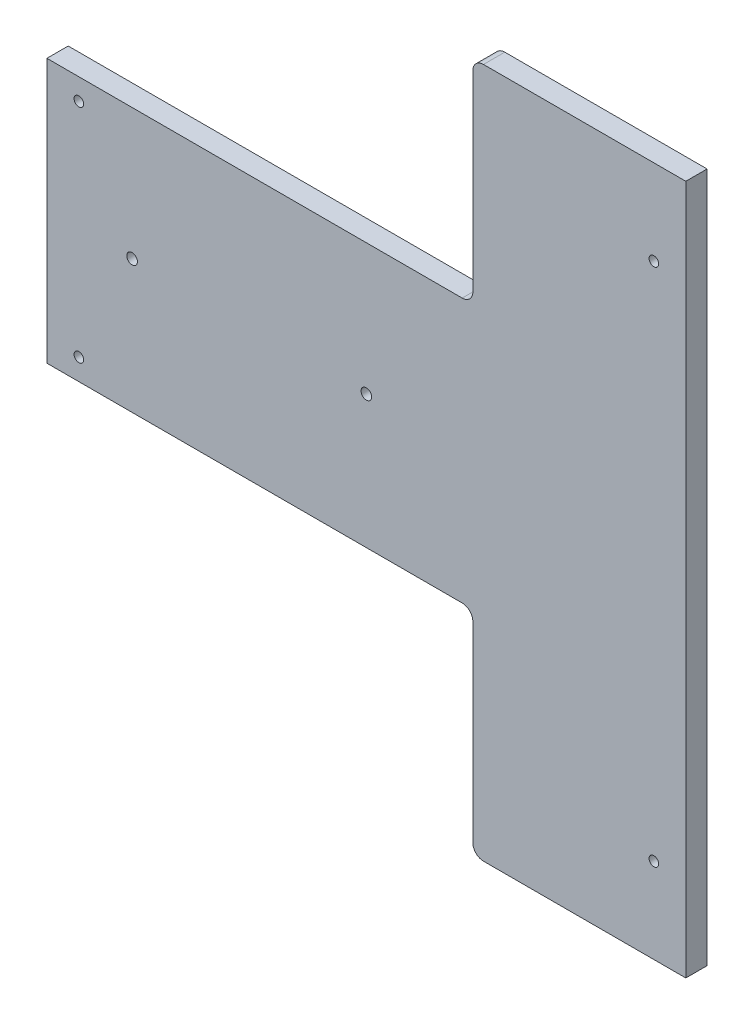
SolidWorks part; units mm, degrees
ref_plane "Plan de face" through (0, 0, 0) normal (0, 0, 1) x (1, 0, 0)
ref_plane "Plan de dessus" through (0, 0, 0) normal (0, 1, 0) x (1, 0, 0)
ref_plane "Plan de droite" through (0, 0, 0) normal (1, 0, 0) x (0, 0, -1)
sketch "Esquisse1" plane through (0, 0, 0) normal (0, 0, 1) x (1, 0, 0)
  line L1 (-122.4446, 41.9355) -> (177.5554, 41.9355)
  line L2 (-122.4446, 41.9355) -> (-122.4446, -82.0645)
  line L3 (-122.4446, -82.0645) -> (177.5554, -82.0645)
  line L4 (177.5554, 41.9355) -> (177.5554, -82.0645)
  line L5 (177.5554, -82.0645) -> (77.5554, -82.0645)
  line L6 (177.5554, -82.0645) -> (177.5554, -182.0645)
  line L7 (177.5554, -182.0645) -> (77.5554, -182.0645)
  line L8 (77.5554, -82.0645) -> (77.5554, -182.0645)
  line L9 (177.5554, 41.9355) -> (77.5554, 41.9355)
  line L10 (177.5554, 41.9355) -> (177.5554, 141.9355)
  line L11 (177.5554, 141.9355) -> (77.5554, 141.9355)
  line L12 (77.5554, 41.9355) -> (77.5554, 141.9355)
  dimension "D1" = 300
  dimension "D2" = 124
  dimension "D3" = 100
  dimension "D4" = 100
  dimension "D5" = 100
  dimension "D6" = 100
extrude "Boss.-Extru.1" add sketch "Esquisse1" along normal blind 10 contours L10 L1 L5 L7 | L4 L1 L2 L3 | L3 L12 L8 L6 region at (27.5554, -20.0645, 0) region at (127.5554, 91.9355, 0) region at (127.5554, -132.0645, 0)
sketch "Esquisse2" plane through (0, 0, 0) normal (0, 0, -1) x (-1, 0, 0)
  line L0 (-177.5554, -182.0645) -> (-177.5554, 141.9355) construction
  line L1 (-177.5554, -182.0645) -> (-77.5554, -182.0645) construction
  line L2 (-177.5554, 141.9355) -> (-77.5554, 141.9355) construction
  line L3 (122.4446, 41.9355) -> (122.4446, -82.0645) construction
  line L4 (122.4446, 41.9355) -> (-77.5554, 41.9355) construction
  line L5 (122.4446, -82.0645) -> (-77.5554, -82.0645) construction
  circle A0 centre (-162.5554, -142.0645) radius 2.25
  circle A1 centre (-162.5554, 101.9355) radius 2.25
  circle A2 centre (107.4446, 31.9355) radius 2.25
  circle A3 centre (107.4446, -72.0645) radius 2.25
  dimension "D1" = 4.5
  dimension "D2" = 4.5
  dimension "D3" = 4.5
  dimension "D4" = 4.5
  dimension "D5" = 15
  dimension "D6" = 40
  dimension "D7" = 40
  dimension "D8" = 15
  dimension "D10" = 10
  dimension "D11" = 15
  dimension "D12" = 10
  dimension "D9" = 15
extrude "Enlèv. mat.-Extru.1" cut sketch "Esquisse2" against normal blind 10
sketch "Esquisse3" plane through (0, 0, 0) normal (0, 0, -1) x (-1, 0, 0)
  line L0 (122.4446, -82.0645) -> (-77.5554, -82.0645) construction
  line L1 (122.4446, 41.9355) -> (122.4446, -82.0645) construction
  circle A0 centre (-27.5554, -19.5645) radius 2.5
  circle A1 centre (82.4446, -19.5645) radius 2.5
  dimension "D1" = 5
  dimension "D2" = 5
  dimension "D3" = 62.5
  dimension "D4" = 62.5
  dimension "D5" = 40
  dimension "D6" = 110
extrude "Enlèv. mat.-Extru.2" cut sketch "Esquisse3" against normal blind 10
fillet "Congé1" radius 5 4 edges at (77.5554, 141.9355, 5) (77.5554, 41.9355, 5) (77.5554, -82.0645, 5) (77.5554, -182.0645, 5)
